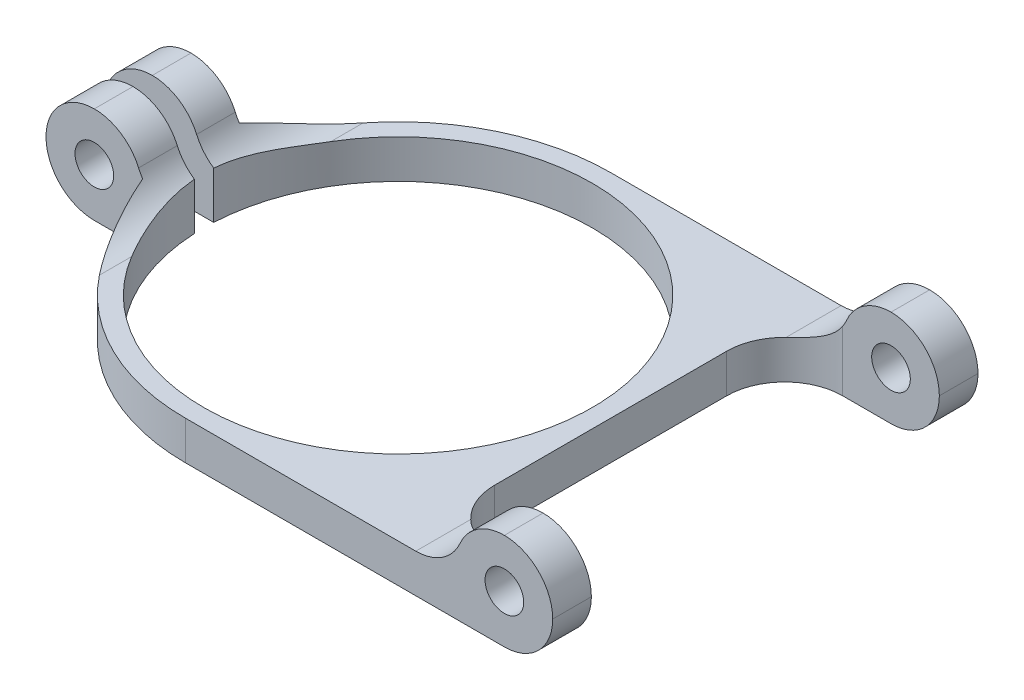
SolidWorks part; units mm, degrees
ref_plane "Front Plane" through (0, 0, 0) normal (0, 0, 1) x (1, 0, 0)
ref_plane "Top Plane" through (0, 0, 0) normal (0, 1, 0) x (1, 0, 0)
ref_plane "Right Plane" through (0, 0, 0) normal (1, 0, 0) x (0, 0, -1)
sketch "Sketch1" plane through (0, 0, 0) normal (0, 1, 0) x (1, 0, 0)
  line L0 (0, 55) -> (70, 55)
  line L1 (70, 55) -> (95, 55)
  line L2 (95, 55) -> (95, 45)
  line L3 (95, 45) -> (70, 45)
  line L4 (70, -45) -> (95, -45)
  line L5 (95, -45) -> (95, -55)
  line L6 (95, -55) -> (70, -55)
  line L7 (70, -55) -> (0, -55)
  line L8 (95, 0) -> (0, 0) construction
  line L9 (55, -30) -> (55, 30)
  arc A0 (0, 55) -> (0, -55) centre (0, 0) ccw
  circle A2 centre (0, 0) radius 50.25
  arc A3 (70, -45) -> (55, -30) centre (70, -30) cw
  arc A4 (70, 45) -> (55, 30) centre (70, 30) ccw
  point P17 (106.6338, 45)
  point P19 (55, 0)
  point P20 (0, 0)
  dimension "D1" = 110
  dimension "D5" = 15
  dimension "D6" = 100.5
  dimension "D2" = 25
  dimension "D3" = 10
  dimension "D4" = 95
  dimension "D7" = 110
  dimension "D8" = 55
extrude "Boss-Extrude1" add sketch "Sketch1" along normal blind 10 contours L8 L3 L2 L1 L0 A0 | L8 A0 L7 L6 L5 L4 region at (35, 0, -53.1399)
sketch "Sketch2" plane through (0, 0, 55) normal (0, 0, 1) x (1, 0, 0)
  line L0 (82.5, 0) -> (82.5, 25) construction
  line L1 (70, 10) -> (95, 10)
  line L2 (70, 10) -> (70, 25)
  line L3 (70, 25) -> (95, 25)
  line L4 (95, 10) -> (95, 25)
  line L5 (95, 0) -> (0, 0) construction
  point P5 (0, 0)
  point P9 (93.3358, 0)
  dimension "D1" = 25
extrude "Boss-Extrude2" add sketch "Sketch2" against normal up to surface (10 mm away) up to face at (82.5, 5, 45)
sketch "Sketch3" plane through (0, 0, -55) normal (0, 0, -1) x (-1, 0, 0)
  line L0 (0, 10) -> (-95, 10) construction
  line L1 (-95, 10) -> (-70, 10)
  line L2 (-95, 10) -> (-95, 25)
  line L3 (-95, 25) -> (-70, 25)
  line L4 (-70, 10) -> (-70, 25)
  line L5 (-95, 25) -> (-70, 25) construction
  line L6 (-70, 25) -> (-70, 10) construction
  point P4 (-80, 10)
  point P6 (-104.5338, 10)
  point P9 (0, 0)
  point P10 (-105, 10)
extrude "Boss-Extrude3" add sketch "Sketch3" against normal up to surface (10 mm away) up to face at (82.5, 5, -45)
fillet "Fillet1" [suppressed] radius 1
sketch "Sketch4" plane through (0, 0, 55) normal (0, 0, 1) x (1, 0, 0)
  line L0 (95, 0) -> (70, 25) construction
  circle A0 centre (82.5, 12.5) radius 5
  point P6 (92.5, 12.5)
  dimension "D1" = 10
extrude "Cut-Extrude1" cut sketch "Sketch4" against normal through all
sketch "Sketch5" plane through (0, 0, 0) normal (0, 1, 0) x (1, 0, 0)
  line L0 (-53.5607, -12.5) -> (-53.5607, 12.5)
  line L1 (-78.5607, 12.5) -> (-53.5607, 12.5)
  line L2 (-78.5607, 12.5) -> (-78.5607, -12.5)
  line L3 (-78.5607, -12.5) -> (-53.5607, -12.5)
  line L5 (-66.0607, -12.5) -> (-66.0607, 12.5) construction
  line L6 (-78.5607, 0) -> (-53.5607, 0) construction
  arc A0 (0, 55) -> (0, -55) centre (0, 0) ccw construction
  arc A1 (-53.5607, 12.5) -> (-53.5607, -12.5) centre (0, 0) ccw construction
  point P3 (-66.0607, 0)
  dimension "D1" = 25
  dimension "D2" = 25
extrude "Boss-Extrude4" add sketch "Sketch5" along normal blind 25
fillet "Fillet2" radius 12.5 9 edges at (70, 25, -50) (95, 0, -50) (95, 25, -50) (95, 0, 50) (95, 25, 50) (70, 25, 50) (-78.5607, 0, 0) (-53.5607, 25, 0) (-78.5607, 25, 0)
fillet "Fillet3" radius 12.5 3 edges at (70, 10, 50) (70, 10, -50) (-53.5607, 10, 0)
sketch "Sketch6" plane through (0, 0, 0) normal (0, 1, 0) x (1, 0, 0)
  line L0 (0, 0) -> (-78.5607, 0) construction
  line L1 (-78.5607, -12.5) -> (-78.5607, 12.5) construction
  line L2 (0, -2.5) -> (-78.5607, -2.5)
  line L3 (0, 2.5) -> (-78.5607, 2.5)
  arc A0 (0, -2.5) -> (0, 2.5) centre (0, 0) ccw
  arc A1 (-78.5607, 2.5) -> (-78.5607, -2.5) centre (-78.5607, 0) ccw
  point P5 (-39.2804, 0)
  dimension "D1" = 5
extrude "Cut-Extrude2" cut sketch "Sketch6" along normal through all
sketch "Sketch7" plane through (0, 0, 0) normal (0, 0, 1) x (1, 0, 0)
  circle A0 centre (-66.0607, 12.5) radius 5
  dimension "D1" = 10
extrude "Cut-Extrude3" cut sketch "Sketch7" against normal through all and the other way through all
